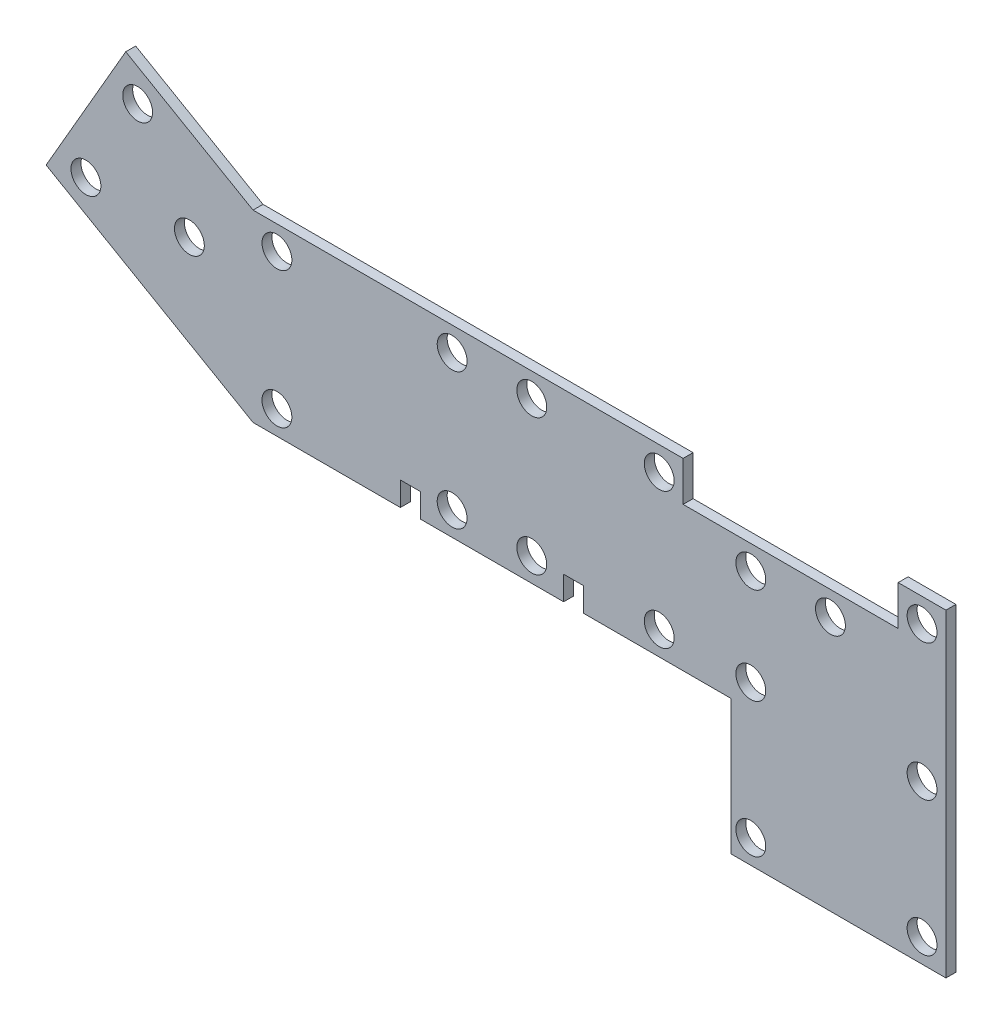
SolidWorks part; units mm, degrees
material "1023 Carbon Steel Sheet (SS)"
ref_plane "Front Plane" through (0, 0, 0) normal (0, 0, 1) x (1, 0, 0)
ref_plane "Top Plane" through (0, 0, 0) normal (0, 1, 0) x (1, 0, 0)
ref_plane "Right Plane" through (0, 0, 0) normal (1, 0, 0) x (0, 0, -1)
sketch "Sketch1" plane through (0, 0, 0) normal (0, 0, 1) x (1, 0, 0)
  line L0 (0, 0) -> (-40.5911, 23.4353)
  line L1 (-40.5911, 23.4353) -> (-65.9911, -20.5588)
  line L2 (-65.9911, -20.5588) -> (0, -58.6588)
  line L3 (0, -58.6588) -> (46.99, -58.6588)
  line L4 (46.99, -58.6588) -> (46.99, -51.0388)
  line L5 (46.99, -51.0388) -> (53.34, -51.0388)
  line L6 (53.34, -51.0388) -> (53.34, -58.6588)
  line L7 (53.34, -58.6588) -> (99.06, -58.6588)
  line L8 (99.06, -58.6588) -> (99.06, -51.0388)
  line L9 (99.06, -51.0388) -> (105.41, -51.0388)
  line L10 (105.41, -51.0388) -> (105.41, -58.6588)
  line L11 (105.41, -58.6588) -> (152.4, -58.6588)
  line L12 (152.4, -58.6588) -> (152.4, -101.6)
  line L13 (152.4, -101.6) -> (220.98, -101.6)
  line L14 (220.98, -101.6) -> (220.98, 0)
  line L15 (220.98, 0) -> (205.74, 0)
  line L16 (205.74, 0) -> (205.74, -12.7)
  line L17 (205.74, -12.7) -> (137.16, -12.7)
  line L18 (137.16, -12.7) -> (137.16, 0)
  line L19 (137.16, 0) -> (99.06, 0)
  line L23 (99.06, 0) -> (0, 0)
  circle A1 centre (-20.2956, -17.6117) radius 4.7625
  circle A2 centre (-53.2911, -17.6117) radius 4.7625
  circle A3 centre (-36.7934, 10.9633) radius 4.7625
  circle A4 centre (-36.7934, -8.0867) radius 19.05 construction
  circle A5 centre (7.62, -51.0388) radius 4.7625
  circle A6 centre (7.62, -7.62) radius 4.7625
  circle A7 centre (63.5, -7.62) radius 4.7625
  circle A8 centre (88.9, -7.62) radius 4.7625
  circle A9 centre (129.54, -7.62) radius 4.7625
  circle A10 centre (88.9, -51.0388) radius 4.7625
  circle A11 centre (63.5, -51.0388) radius 4.7625
  circle A12 centre (129.54, -51.0388) radius 4.7625
  circle A13 centre (158.75, -20.32) radius 4.7625
  circle A14 centre (184.15, -20.32) radius 4.7625
  circle A15 centre (213.36, -7.62) radius 4.7625
  circle A16 centre (213.36, -93.98) radius 4.7625
  circle A17 centre (158.75, -93.98) radius 4.7625
  circle A18 centre (213.36, -51.0388) radius 4.7625
  circle A19 centre (158.75, -51.0388) radius 4.7625
  point P3 (-36.7934, -8.0867)
  point P24 (171.45, -12.7)
  point P28 (-53.2911, 1.4383)
  point P33 (76.2, -58.6588)
  point P36 (9.0728, -51.0388)
  point P39 (9.0728, -6.8369)
  point P42 (64.751, -6.8369)
  point P45 (85.8632, -6.8369)
  point P48 (123.12, -6.8369)
  point P51 (0, 0)
  point P52 (0, 0)
  point P53 (91.0378, -52.787)
  point P56 (64.751, -52.787)
  point P57 (85.8632, -52.787)
  point P60 (123.12, -52.787)
  point P61 (9.0728, -52.787)
  point P64 (154.1674, -20.5588)
  point P67 (177.7634, -20.5588)
  point P70 (205.706, -6.8369)
  point P73 (205.706, -95.4253)
  point P76 (158.928, -95.4253)
  point P79 (205.706, -52.787)
  point P82 (154.1674, -52.787)
  point P83 (0, 0)
  point P84 (0, 0)
  point P85 (0, 0)
  point P86 (0, 0)
  point P87 (0, 0)
  point P88 (0, 0)
  point P89 (0, 0)
  point P90 (0, 0)
  point P91 (0, 0)
  point P92 (0, 0)
  point P93 (0, 0)
  point P94 (158.307, -20.5588)
  point P95 (171.7609, -20.5588)
  point P96 (0, 0)
  point P97 (0, 0)
  point P98 (0, 0)
  point P99 (0, 0)
  point P100 (0, 0)
  point P101 (0, 0)
  point P102 (0, 0)
  dimension "D18" = 9.525
  dimension "D21" = 3
  dimension "D16" = 38.1
  dimension "D17" = 7.62
  dimension "D1" = 30
  dimension "D2" = 76.2
  dimension "D3" = 50.8
  dimension "D4" = 76.2
  dimension "D5" = 68.58
  dimension "D6" = 6.35
  dimension "D7" = 6.35
  dimension "D8" = 45.72
  dimension "D9" = 152.4
  dimension "D10" = 7.62
  dimension "D11" = 19.05
  dimension "D12" = 38.1
  dimension "D13" = 101.6
  dimension "D14" = 15.24
  dimension "D15" = 12.7
  dimension "D19" = 19.05
  dimension "D20" = 25.4
  dimension "D22" = 7.62
  dimension "D23" = 7.62
  dimension "D24" = 12.7
  dimension "D25" = 12.7
  dimension "D26" = 7.62
  dimension "D27" = 7.62
  dimension "D28" = 12.7
  dimension "D29" = 12.7
  dimension "D30" = 7.62
  dimension "D31" = 7.62
  dimension "D32" = 7.62
extrude "Boss-Extrude1" add sketch "Sketch1" along normal blind 3.175 contours L19 L23 L0 L1 L2 L3 L4 L5 L6 L7 L8 L9 L10 L11 L12 L13 L14 L15 L16 L17 L18 A19 A18 A17 A16 A15 A14 A13 A12 A11 A10 A9 A8 A7 A6 A5 region at (96.1905, -36.5089, 0)
